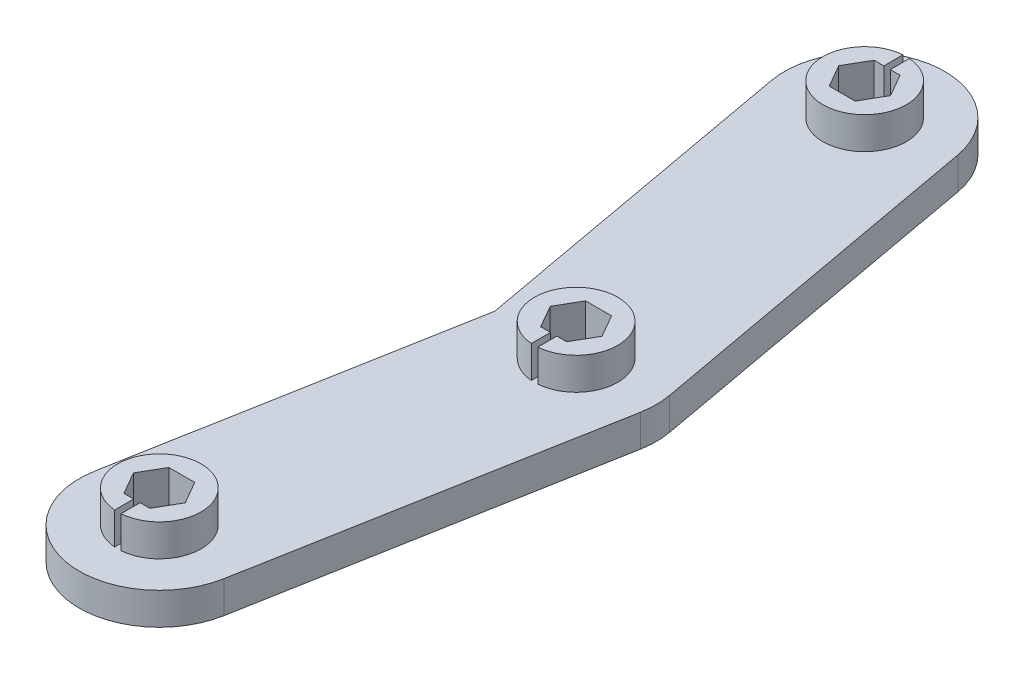
SolidWorks part; units mm, degrees
ref_plane "Alzado" through (0, 0, 0) normal (0, 0, 1) x (1, 0, 0)
ref_plane "Planta" through (0, 0, 0) normal (0, 1, 0) x (1, 0, 0)
ref_plane "Vista lateral" through (0, 0, 0) normal (1, 0, 0) x (0, 0, -1)
sketch "Croquis1" plane through (0, 0, 0) normal (0, 1, 0) x (1, 0, 0)
  line L0 (-110.263, 0) -> (110.263, 0) construction
  line L5 (0, -156.6248) -> (0, 156.6248) construction
  line L6 (-44.5967, 105.5279) -> (-25.4099, 0)
  line L7 (4.5967, 114.4721) -> (24.5967, 4.4721)
  line L8 (4.5967, -114.4721) -> (24.5967, -4.4721)
  line L9 (-44.5967, -105.5279) -> (-25.4099, 0)
  arc A0 (24.5967, -4.4721) -> (24.5967, 4.4721) centre (0, 0) ccw
  arc A1 (4.5967, 114.4721) -> (-44.5967, 105.5279) centre (-20, 110) ccw
  arc A3 (4.5967, -114.4721) -> (-44.5967, -105.5279) centre (-20, -110) cw
  point P8 (0, 0)
  point P11 (0, 0)
  point P16 (0, 0)
  point P17 (-23.796, -7.6648)
  dimension "D1" = 50
  dimension "D2" = 110
  dimension "D3" = 40
extrude "Saliente-Extruir1" add sketch "Croquis1" along normal blind 10
sketch "Croquis3" plane through (0, 0, 0) normal (0, 1, 0) x (1, 0, 0)
  line L0 (-88.2271, 0) -> (88.2271, 0) construction
  line L2 (4.0415, -7) -> (8.0829, 0)
  line L3 (8.0829, 0) -> (4.0415, 7)
  line L4 (4.0415, 7) -> (-4.0415, 7)
  line L5 (-4.0415, 7) -> (-8.0829, 0)
  line L6 (-8.0829, 0) -> (-4.0415, -7)
  line L7 (-4.0415, -7) -> (4.0415, -7)
  line L8 (-15.9585, 103) -> (-11.9171, 110)
  line L9 (-11.9171, 110) -> (-15.9585, 117)
  line L10 (-15.9585, 117) -> (-24.0415, 117)
  line L11 (-24.0415, 117) -> (-28.0829, 110)
  line L12 (-28.0829, 110) -> (-24.0415, 103)
  line L13 (-24.0415, 103) -> (-15.9585, 103)
  line L14 (-15.9585, -117) -> (-11.9171, -110)
  line L15 (-11.9171, -110) -> (-15.9585, -103)
  line L16 (-15.9585, -103) -> (-24.0415, -103)
  line L17 (-24.0415, -103) -> (-28.0829, -110)
  line L18 (-28.0829, -110) -> (-24.0415, -117)
  line L19 (-24.0415, -117) -> (-15.9585, -117)
  circle A0 centre (0, 0) radius 5 construction
  circle A2 centre (-20, 110) radius 5 construction
  circle A3 centre (-20, -110) radius 5 construction
  arc A4 (4.5967, 114.4721) -> (-44.5967, 105.5279) centre (-20, 110) ccw construction
  circle A5 centre (0, 0) radius 7 construction
  circle A6 centre (-20, 110) radius 7 construction
  circle A7 centre (-20, -110) radius 7 construction
  point P9 (0, 0)
  dimension "D1" = 14
extrude "Cortar-Extruir1" cut sketch "Croquis3" along normal through all both and the other way through all
sketch "Croquis4" plane through (0, 10, 0) normal (0, -1, 0) x (1, 0, 0)
  line L0 (-88.2271, 0) -> (88.2271, 0) construction
  line L7 (-11.9171, 110) -> (-15.9585, 103) construction
  line L8 (-15.9585, 117) -> (-11.9171, 110) construction
  line L9 (-15.9585, 103) -> (-24.0415, 103) construction
  line L10 (-24.0415, 103) -> (-28.0829, 110) construction
  line L11 (-28.0829, 110) -> (-24.0415, 117) construction
  line L12 (-24.0415, 117) -> (-15.9585, 117) construction
  line L13 (-11.9171, 110) -> (-15.9585, 103)
  line L14 (-15.9585, 117) -> (-11.9171, 110)
  line L15 (-15.9585, 103) -> (-24.0415, 103)
  line L16 (-24.0415, 103) -> (-28.0829, 110)
  line L17 (-28.0829, 110) -> (-24.0415, 117)
  line L18 (-24.0415, 117) -> (-21, 117)
  line L32 (4.0415, 7) -> (8.0829, 0) construction
  line L39 (8.0829, 0) -> (4.0415, -7) construction
  line L40 (4.0415, -7) -> (-4.0415, -7) construction
  line L41 (-4.0415, -7) -> (-8.0829, 0) construction
  line L42 (-8.0829, 0) -> (-4.0415, 7) construction
  line L43 (-4.0415, 7) -> (4.0415, 7) construction
  line L44 (4.0415, 7) -> (8.0829, 0)
  line L45 (8.0829, 0) -> (4.0415, -7)
  line L46 (4.0415, -7) -> (-4.0415, -7)
  line L47 (-4.0415, -7) -> (-8.0829, 0)
  line L48 (-8.0829, 0) -> (-4.0415, 7)
  line L49 (-4.0415, 7) -> (-1, 7)
  line L50 (-20, 117) -> (-20, 123) construction
  line L51 (-21, 117) -> (-21, 122.9615)
  line L52 (-19, 117) -> (-19, 122.9615)
  line L53 (-19, 117) -> (-15.9585, 117)
  line L54 (5.5, 0) -> (-5.5, 0) construction
  line L55 (-21, -117) -> (-21, -122.9615)
  line L56 (-19, -117) -> (-19, -122.9615)
  line L57 (-19, -117) -> (-15.9585, -117)
  line L58 (-24.0415, -117) -> (-21, -117)
  line L59 (-28.0829, -110) -> (-24.0415, -117)
  line L60 (-24.0415, -103) -> (-28.0829, -110)
  line L61 (-15.9585, -103) -> (-24.0415, -103)
  line L62 (-11.9171, -110) -> (-15.9585, -103)
  line L63 (-15.9585, -117) -> (-11.9171, -110)
  line L64 (0, 7) -> (0, 13) construction
  line L65 (-1, 7) -> (-1, 12.9615)
  line L66 (1, 7) -> (1, 12.9615)
  line L67 (1, 7) -> (4.0415, 7)
  arc A0 (-21, 122.9615) -> (-19, 122.9615) centre (-20, 110) ccw
  arc A2 (-1, 12.9615) -> (1, 12.9615) centre (0, 0) ccw
  arc A3 (-21, -122.9615) -> (-19, -122.9615) centre (-20, -110) cw
  dimension "D1" = 26
  dimension "D2" = 2
  dimension "D3" = 2
extrude "Saliente-Extruir2" add sketch "Croquis4" against normal blind 10
